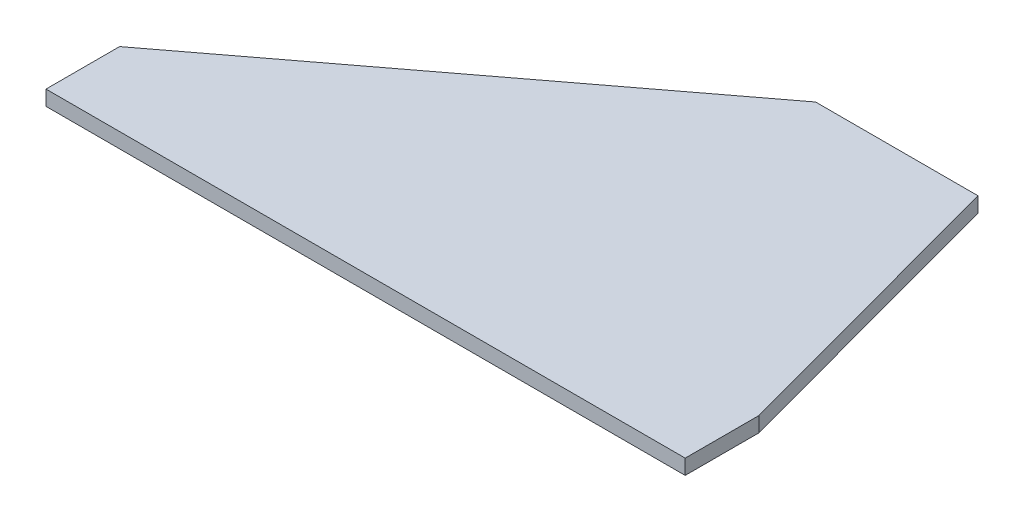
SolidWorks part; units mm, degrees
ref_plane "Front Plane" through (0, 0, 0) normal (0, 0, 1) x (1, 0, 0)
ref_plane "Top Plane" through (0, 0, 0) normal (0, 1, 0) x (1, 0, 0)
ref_plane "Right Plane" through (0, 0, 0) normal (1, 0, 0) x (0, 0, -1)
sketch "Sketch1" plane through (0, 0, 0) normal (0, 1, 0) x (1, 0, 0)
  line L0 (0, 0) -> (0, 23.368)
  line L1 (0, 23.368) -> (125.73, 118.618)
  line L2 (125.73, 118.618) -> (177.292, 118.618)
  line L3 (177.292, 118.618) -> (202.946, 23.368)
  line L4 (202.946, 23.368) -> (202.946, 0)
  line L5 (202.946, 0) -> (0, 0)
  line L6 (0, 23.368) -> (0, 118.618) construction
  line L7 (0, 118.618) -> (125.73, 118.618) construction
  dimension "D1" = 202.946
  dimension "D2" = 23.368
  dimension "D3" = 51.562
  dimension "D4" = 95.25
  dimension "D5" = 125.73
extrude "Boss-Extrude1" add sketch "Sketch1" along normal blind 2.3813 and the other way blind 2.3813 contours L3 L4 L5 L0 L1 L2
equation "\"Root Chord\"=7.99"
equation "\"Tip Chord\"=2.03"
equation "\"Height\"=3.75"
equation "\"Sweep Length\"=4.95"
equation "\"Fin Thickness\"= 3 / 16"
equation "\"Bevel Depth\"= 1 / 16"
equation "\"Bevel Width\"= 1 / 4"
equation "\"Tab Height\"=0.92"
equation "\"D2@Sketch1\"=\"Tab Height\""
equation "\"D4@Sketch1\"=\"Height\""
equation "\"D5@Sketch1\"=\"Sweep Length\""
equation "\"D3@Sketch1\"=\"Tip Chord\""
equation "\"D1@Sketch1\"=\"Root Chord\""
equation "\"D1@Boss-Extrude1\"=\"Fin Thickness\"/2"
equation "\"D2@Boss-Extrude1\"=\"Fin Thickness\"/2"
equation "\"D1@Chamfer2\"=\"Bevel Depth\""
equation "\"D3@Chamfer2\"=\"Bevel Width\""
